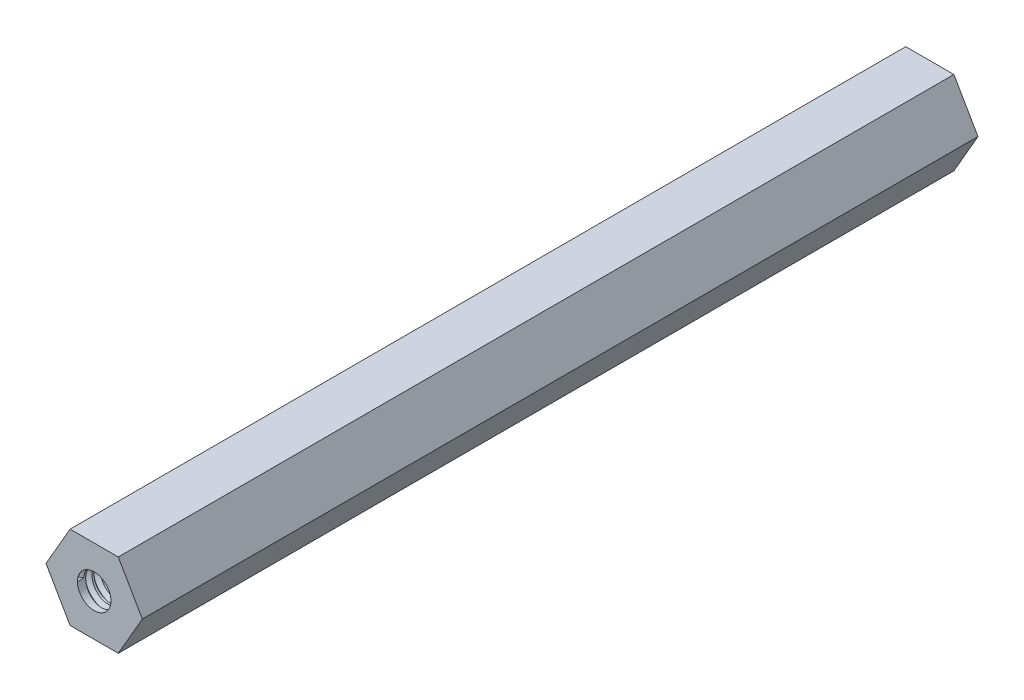
SolidWorks part; units mm, degrees
material "7075-T6 (SN)"
ref_plane "Alzado" through (0, 0, 0) normal (0, 0, 1) x (1, 0, 0)
ref_plane "Planta" through (0, 0, 0) normal (0, 1, 0) x (1, 0, 0)
ref_plane "Vista lateral" through (0, 0, 0) normal (1, 0, 0) x (0, 0, -1)
sketch "Croquis2" plane through (0, 0, 0) normal (0, 0, 1) x (1, 0, 0)
  line L1 (3.6662, -6.35) -> (7.3323, 0)
  line L2 (7.3323, 0) -> (3.6662, 6.35)
  line L3 (3.6662, 6.35) -> (-3.6662, 6.35)
  line L4 (-3.6662, 6.35) -> (-7.3323, 0)
  line L5 (-7.3323, 0) -> (-3.6662, -6.35)
  line L6 (-3.6662, -6.35) -> (3.6662, -6.35)
  circle A0 centre (0, 0) radius 6.35 construction
  dimension "D1" = 12.7
extrude "Extrusión Hex Profile" add sketch "Croquis2" along normal mid plane 127.171
sketch "Croquis3" plane through (0, 0, 0) normal (0, 0, 1) x (1, 0, 0)
  circle A0 centre (0, 0) radius 2.5527
  dimension "D1" = 5.1054
extrude "Tap Hole 1" cut sketch "Croquis3" against normal blind 19.05 from surface starting at face at (0, 0, 63.5855)
extrude "Tap Hole 2" cut sketch "Croquis3<3>" along normal blind 19.05 from surface starting at face at (0, 0, -63.5855)
sketch "Croquis3<3>" plane through (0, 0, 0) normal (0, 0, 1) x (1, 0, 0) same geometry as "Croquis3"
sketch "Croquis7" plane through (0, 0, 0) normal (0, 0, 1) x (1, 0, 0)
  circle A0 centre (0, 0) radius 6.8707
  dimension "D1" = 13.7414
extrude "ThunderHex" [suppressed] cut sketch "Croquis7" against normal through all both and the other way through all flip side to cut
sketch "Croquis8" plane through (0, 0, 0) normal (0, 1, 0) x (1, 0, 0)
  line L0 (0, -63.5855) -> (-5.5562, -63.5855) construction
  line L1 (3.6662, -63.5855) -> (-3.6662, -63.5855) construction
  line L3 (0, -63.5855) -> (0, 0) construction
  line L4 (-5.5562, -63.5855) -> (-6.35, -62.7917)
  line L5 (-6.35, -62.7917) -> (-6.35, -61.998)
  line L6 (-6.35, -61.998) -> (-5.9055, -61.998)
  line L7 (-5.9055, -61.998) -> (-5.9055, -60.4105)
  line L8 (-5.9055, -60.4105) -> (-12.7, -60.4105)
  line L9 (-12.7, -60.4105) -> (-12.7, -63.5855)
  line L10 (-12.7, -63.5855) -> (-5.5562, -63.5855)
  line L11 (-3.6662, -63.5855) -> (-7.3323, -63.5855) construction
  dimension "D1" = 11.811
  dimension "D2" = 12.7
  dimension "D3" = 45
  dimension "D4" = 0.7937
  dimension "D6" = 0.7937
  dimension "D7" = 3.175
  dimension "D8" = 25.4
revolve "Retaining Ring 1" [suppressed] cut sketch "Croquis8" angle 360 about L3
sketch "Croquis9" plane through (0, 0, 0) normal (0, -1, 0) x (1, 0, 0)
  line L0 (0, -63.5855) -> (-5.5562, -63.5855) construction
  line L3 (0, -63.5855) -> (0, 0) construction
  line L4 (-5.5562, -63.5855) -> (-6.35, -62.7917)
  line L5 (-6.35, -62.7917) -> (-6.35, -61.998)
  line L6 (-6.35, -61.998) -> (-5.9055, -61.998)
  line L7 (-5.9055, -61.998) -> (-5.9055, -60.4105)
  line L8 (-5.9055, -60.4105) -> (-12.7, -60.4105)
  line L9 (-12.7, -60.4105) -> (-12.7, -63.5855)
  line L10 (-12.7, -63.5855) -> (-5.5562, -63.5855)
  line L12 (-3.6662, -63.5855) -> (3.6662, -63.5855) construction
  line L13 (-7.3323, -63.5855) -> (-3.6662, -63.5855) construction
  dimension "D1" = 11.811
  dimension "D2" = 12.7
  dimension "D3" = 45
  dimension "D4" = 0.7937
  dimension "D6" = 0.7937
  dimension "D7" = 3.175
  dimension "D8" = 25.4
revolve "Retaining Ring 2" [suppressed] cut sketch "Croquis9" angle 360 about L3
sketch "Croquis10" plane through (0, 0, 0) normal (0, 1, 0) x (1, 0, 0)
  line L0 (0, -63.5855) -> (0, 0) construction
  line L1 (3.6662, -63.5855) -> (-3.6662, -63.5855) construction
  line L2 (0, -63.5855) -> (-5.5562, -63.5855) construction
  line L3 (-3.6662, -63.5855) -> (-7.3323, -63.5855) construction
  line L4 (-5.5562, -63.5855) -> (-6.35, -62.7917)
  line L5 (-6.35, -62.7917) -> (-6.35, -55.6353)
  line L6 (-6.35, -55.6353) -> (-9.525, -55.6353)
  line L7 (-9.525, -55.6353) -> (-9.525, -63.5855)
  line L8 (-9.525, -63.5855) -> (-5.5562, -63.5855)
  dimension "D2" = 12.7
  dimension "D1" = 45
  dimension "D3" = 0.7937
  dimension "D4" = 7.9502
  dimension "D5" = 19.05
revolve "Round End 1" [suppressed] cut sketch "Croquis10" angle 360 about L0
sketch "Croquis12" plane through (0, 0, 0) normal (0, -1, 0) x (1, 0, 0)
  line L0 (0, -63.5855) -> (0, 0) construction
  line L2 (0, -63.5855) -> (-5.5562, -63.5855) construction
  line L4 (-5.5562, -63.5855) -> (-6.35, -62.7917)
  line L5 (-6.35, -62.7917) -> (-6.35, -55.6353)
  line L6 (-6.35, -55.6353) -> (-9.525, -55.6353)
  line L7 (-9.525, -55.6353) -> (-9.525, -63.5855)
  line L8 (-9.525, -63.5855) -> (-5.5562, -63.5855)
  line L9 (-3.6662, -63.5855) -> (3.6662, -63.5855) construction
  dimension "D1" = 45
  dimension "D3" = 0.7937
  dimension "D4" = 7.9502
  dimension "D2" = 12.7
  dimension "D5" = 19.05
revolve "Round End 2" [suppressed] cut sketch "Croquis12" angle 360 about L0
thread "Rosca1" pitch 1.27 method cut profile "Perfil de rosca1" start angle 0, offset 0, length 0, pitch 1.27, diameter 5.1054
ref_plane "Plano1" through (2.5527, 0, -63.5855) normal (0, -1, 0) x (1, 0, 0)
sketch "Perfil de rosca1" plane through (2.5527, 0, -63.5855) normal (0, -1, 0) x (1, 0, 0)
  line L0 (0, 0) -> (0, 1.27) construction
  line L1 (0, 0) -> (0.6874, 0.3969)
  line L2 (0.6874, 0.3969) -> (0.6874, 0.5556)
  line L3 (0.6874, 0.5556) -> (0, 0.9525)
  line L4 (0.6874, 0.4762) -> (0, 0.4762) construction
  line L11 (0, 0) -> (0, 0.9525)
  point P2 (0, 0)
  dimension "Pitch" = 1.27
  dimension "Profile_Angle" = 60
  dimension "Profile_Land" = 0.1588
  dimension "Profile_Height" = 0.6874
thread "Rosca2" pitch 1.27 method cut profile "Perfil de rosca2" start angle 0, offset 0, length 0, pitch 1.27, diameter 5.1054
ref_plane "Plano2" through (-2.5527, 0, 63.5855) normal (0, -1, 0) x (-1, 0, 0)
sketch "Perfil de rosca2" plane through (-2.5527, 0, 63.5855) normal (0, -1, 0) x (-1, 0, 0)
  line L0 (0, 0) -> (0, 1.27) construction
  line L1 (0, 0) -> (0.6874, 0.3969)
  line L2 (0.6874, 0.3969) -> (0.6874, 0.5556)
  line L3 (0.6874, 0.5556) -> (0, 0.9525)
  line L4 (0.6874, 0.4762) -> (0, 0.4762) construction
  line L11 (0, 0) -> (0, 0.9525)
  point P2 (0, 0)
  dimension "Pitch" = 1.27
  dimension "Profile_Angle" = 60
  dimension "Profile_Land" = 0.1588
  dimension "Profile_Height" = 0.6874
equation "\"HexOD\"= 0.5pulgadas"
equation "\"Largo\"= 5.00673228"
equation "\"D1@Croquis2\"=\"HexOD\""
equation "\"D1@Extrusión Hex Profile\" = \"Largo\""
equation "\"TapHole\"= IIF ( \"HexOD\" = 0.5pulgadas , 0.2010pulgadas , 0.190pulgadas )"
equation "\"D1@Croquis3\"=\"TapHole\""
equation "\"ProTapHole\"= 0.75pulgadas"
equation "\"D1@Tap Hole 1\" = \"ProTapHole\""
equation "\"D1@Tap Hole 2\" = \"ProTapHole\""
equation "\"ThunderHex\"= IIF ( \"HexOD\" = 0.5pulgadas , 0.541pulgadas , 0.4035pulgadas )"
equation "\"D1@Croquis7\"=\"ThunderHex\""
equation "\"D2@Croquis8\"=\"HexOD\""
equation "\"D1@Croquis8\"=if(\"HexOD\"=0.5pulgadas, 0.465pulgadas, 0.35pulgadas )"
equation "\"D2@Croquis9\"=\"HexOD\""
equation "\"D1@Croquis9\"=if(\"HexOD\"=0.5pulgadas, 0.465pulgadas, 0.35pulgadas )"
equation "\"D8@Croquis8\"=\"HexOD\"*2"
equation "\"D8@Croquis9\"=\"HexOD\"*2"
equation "\"D5@Croquis10\"=\"HexOD\"*1.5"
equation "\"D5@Croquis12\"=\"HexOD\"*1.5"
equation "\"D4@Croquis10\"=if( \"D2@Croquis10\"=<0.375, 0.28, 0.313)"
equation "\"D4@Croquis12\"=if( \"D2@Croquis10\"=<0.375, 0.28, 0.313)"
